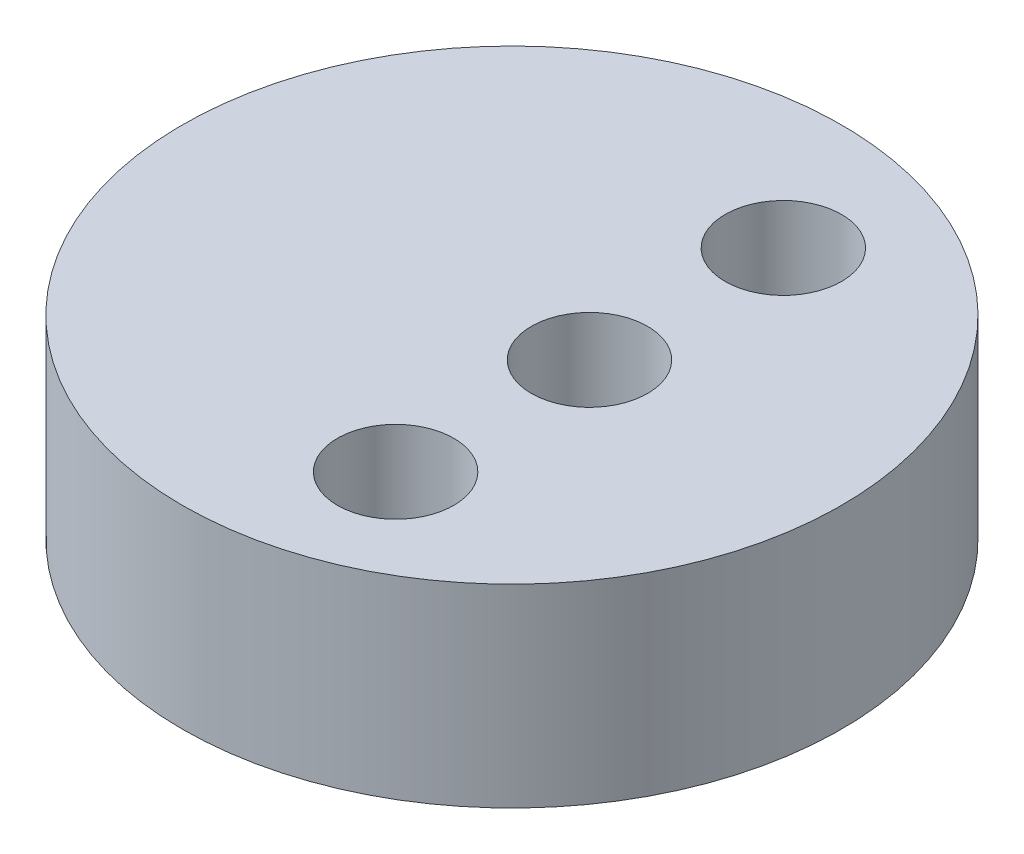
SolidWorks part; units mm, degrees
ref_plane "Front Plane" through (0, 0, 0) normal (0, 0, 1) x (1, 0, 0)
ref_plane "Top Plane" through (0, 0, 0) normal (0, 1, 0) x (1, 0, 0)
ref_plane "Right Plane" through (0, 0, 0) normal (1, 0, 0) x (0, 0, -1)
sketch "Sketch1" plane through (0, 0, 0) normal (0, 1, 0) x (1, 0, 0)
  line L0 (0, 0) -> (-2, 0) construction
  circle A0 centre (0, 0) radius 5 construction
  circle A1 centre (-2, 0) radius 8.5
  circle A2 centre (0, 0) radius 1.5
  circle A3 centre (0, 5) radius 1.5
  circle A4 centre (0, -5) radius 1.5
  point P12 (0, 0)
  dimension "D1" = 10
  dimension "D3" = 17
  dimension "D4" = 3
  dimension "D5" = 3
  dimension "D2" = 2
  dimension "D6" = 2
extrude "Boss-Extrude1" add sketch "Sketch1" along normal blind 5
